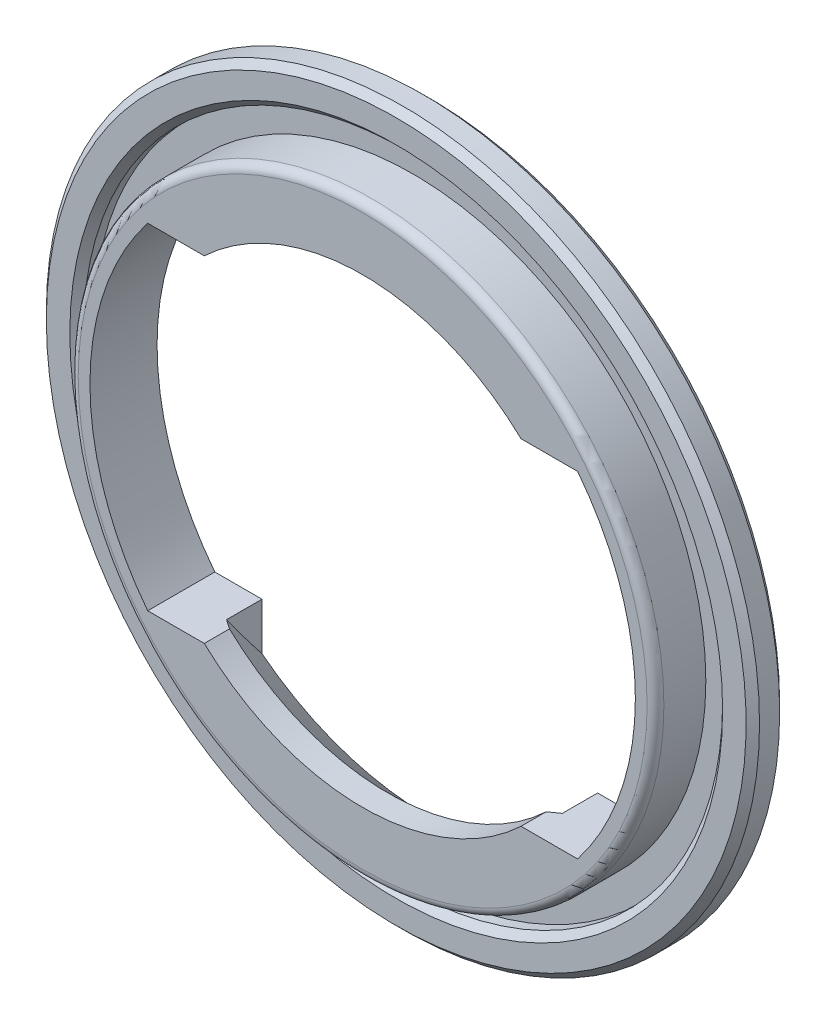
SolidWorks part; units mm, degrees
ref_plane "Ebene vorne" through (0, 0, 0) normal (0, 0, 1) x (1, 0, 0)
ref_plane "Ebene oben" through (0, 0, 0) normal (0, 1, 0) x (1, 0, 0)
ref_plane "Ebene rechts" through (0, 0, 0) normal (1, 0, 0) x (0, 0, -1)
sketch "Skizze3" plane through (0, 0, 0) normal (1, 0, 0) x (0, 0, -1)
  line L0 (-28.0822, 0) -> (28.4247, 0) construction
  line L1 (0, 27.5) -> (0, 34.9)
  line L2 (0, 34.9) -> (6, 34.9)
  line L3 (6, 34.9) -> (6, 38.1)
  line L4 (6, 38.1) -> (4, 38.1)
  line L5 (4, 38.1) -> (4, 42.5)
  line L6 (4, 42.5) -> (8, 42.5)
  line L8 (8, 27.5) -> (0, 27.5)
  line L9 (8, 42.5) -> (8, 27.5)
  dimension "D1" = 55
  dimension "D2" = 69.8
  dimension "D3" = 76.2
  dimension "D4" = 2
  dimension "D5" = 8
  dimension "D6" = 4
  dimension "D7" = 85
revolve "Rotation1" add sketch "Skizze3" angle 360 about L0
chamfer "Fase1" distance 0.8 4 edges at (38.1, 0, -4) (27.5, 0, -8) (42.5, 0, -8) (42.5, 0, -4)
sketch "Skizze4" plane through (0, 0, 0) normal (0, 0, 1) x (1, 0, 0)
  line L0 (-25.6174, 20) -> (25.6174, 20)
  line L1 (-32.5, 0) -> (32.5, 0) construction
  line L2 (-25.6174, -20) -> (25.6174, -20)
  circle A0 centre (0, 0) radius 32.5
  point P5 (29.6518, 13.3049)
  point P9 (0, 0)
  point P10 (-28.2092, 11.597)
  point P11 (-30.397, 11.5008)
  point P12 (28.4357, 11.03)
  dimension "D1" = 65
  dimension "D2" = 40
extrude "Schnitt-Linear austragen1" cut sketch "Skizze4" against normal blind 10 contours A0 L1 L0 | L1 A0 L2 region at (0, 9.6311, 0) region at (0, -9.6311, 0)
sketch "Skizze5" plane through (0, 0, -8) normal (0, 0, -1) x (-1, 0, 0)
  line L0 (0, 32.5) -> (0, -32.5) construction
  line L1 (20, 25.6174) -> (20, -25.6174)
  line L2 (-20, 25.6174) -> (-20, -25.6174)
  circle A0 centre (0, 0) radius 32.5 construction
  circle A1 centre (0, 0) radius 32.5
  line M6 (20.0222, 20) -> (25.6174, 20)
  line M8 (25.6174, -20) -> (20.0222, -20)
  arc M9 (20.0222, -20) -> (-20.0222, -20) centre (0, 0) cw
  line M10 (-20.0222, -20) -> (-25.6174, -20)
  line M12 (-25.6174, 20) -> (-20.0222, 20)
  arc M13 (-20.0222, 20) -> (20.0222, 20) centre (0, 0) cw
  dimension "D1" = 40
extrude "Schnitt-Linear austragen2" cut sketch "Skizze5" against normal blind 5 contours L0 A1 L2 M12 M13 | A1 L0 L1 M13 M6 | L0 L2 M13 M12 M10 M9 | L0 L1 M13 M9 M8 M6 | L0 L2 A1 M9 M10 | L0 A1 L1 M9 M8 region at (-10.4574, 27.8336, -8) region at (10.4574, 27.8336, -8) region at (-9.4838, 0, -8) region at (9.4838, 0, -8) region at (-10.4574, -27.8336, -8) region at (10.4574, -27.8336, -8)
chamfer "Fase2" distance 5 angle 45 2 edges at (0, 32.5, -3) (0, -32.5, -3)
fillet "Verrundung1" radius 1 1 edges at (34.9, 0, 0)
